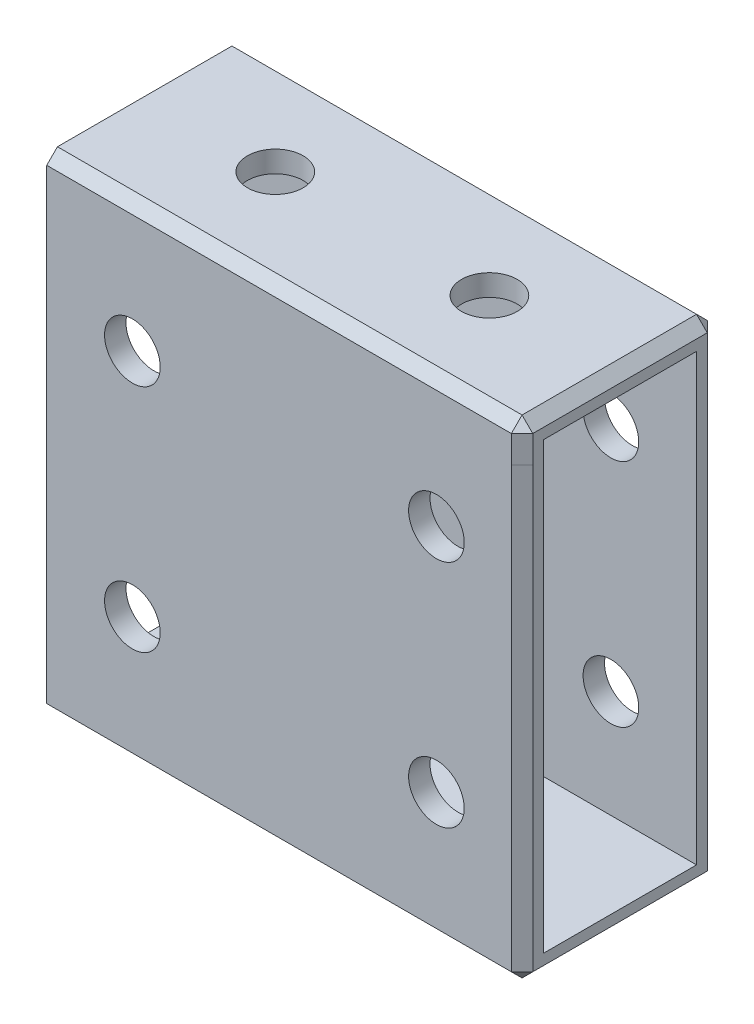
SolidWorks part; units mm, degrees
ref_plane "Front Plane" through (0, 0, 0) normal (0, 0, 1) x (1, 0, 0)
ref_plane "Top Plane" through (0, 0, 0) normal (0, 1, 0) x (1, 0, 0)
ref_plane "Right Plane" through (0, 0, 0) normal (1, 0, 0) x (0, 0, -1)
sketch "Sketch1" plane through (0, 0, 0) normal (0, 0, 1) x (1, 0, 0)
  line L0 (22.2, 40) -> (22.2, 0) construction
  line L1 (0, 0) -> (44.4, 0)
  line L2 (0, 0) -> (0, 40)
  line L3 (0, 40) -> (44.4, 40)
  line L4 (44.4, 0) -> (44.4, 40)
  line L5 (0, 0) -> (8, 0) construction
  line L6 (0, 0) -> (0, 8) construction
  line L10 (8, 29.9769) -> (8, 27.3769) construction
  line L11 (8, 19) -> (8, 8.4769) construction
  line L12 (8, 19) -> (10.573, 19) construction
  line L15 (10.573, 19) -> (10.573, 40) construction
  line L16 (8, 8.4769) -> (36.4, 8.4769) construction
  line L17 (36.4, 8.4769) -> (36.4, 29.9769) construction
  circle A0 centre (8, 8.4769) radius 2.6
  circle A1 centre (8, 29.9769) radius 2.6
  circle A2 centre (36.4, 29.9769) radius 2.6
  circle A3 centre (36.4, 8.4769) radius 2.6
  dimension "D5" = 5.2
  dimension "D6" = 5.2
  dimension "D7" = 5.2
  dimension "D8" = 5.2
  dimension "D1" = 44.4
  dimension "D2" = 40
  dimension "D3" = 21.5
  dimension "D4" = 21.5
  dimension "D9" = 21
  dimension "D10" = 8
  dimension "D11" = 8
extrude "Boss-Extrude1" add sketch "Sketch1" along normal blind 2
sketch "Sketch2" plane through (0, 40, 0) normal (0, 1, 0) x (1, 0, 0)
  line L0 (44.4, -2) -> (44.4, 0) construction
  line L1 (0, -2) -> (44.4, -2)
  line L2 (0, -2) -> (0, 16.3)
  line L3 (0, 16.3) -> (44.4, 16.3)
  line L4 (44.4, -2) -> (44.4, 16.3)
  dimension "D1" = 18.3
  dimension "D2" = 44.4
extrude "Boss-Extrude2" add sketch "Sketch2" along normal blind 2
pattern_linear "LPattern1" count 2 spacing 16.3 along (0, 0, -1) of "Boss-Extrude1"
sketch "Sketch3" plane through (0, 42, 0) normal (0, 1, 0) x (1, 0, 0)
  line L0 (22.2, 16.3) -> (22.2, -2) construction
  line L1 (44.4, 16.3) -> (0, 16.3) construction
  line L2 (0, -2) -> (44.4, -2) construction
  line L3 (22.2, 7.15) -> (12.2, 7.15) construction
  line L4 (22.2, 7.15) -> (32.2, 7.15) construction
  circle A0 centre (12.2, 7.15) radius 2.6
  circle A1 centre (32.2, 7.15) radius 2.6
  dimension "D3" = 5.2
  dimension "D4" = 5.2
  dimension "D1" = 10
  dimension "D2" = 10
extrude "Cut-Extrude1" cut sketch "Sketch3" against normal through all
chamfer "Chamfer1" distance 1 angle 45 11 edges at (22.2, 42, -16.3) (22.2, 42, 2) (0, 0, -15.3) (0, 0, 1) (22.2, 0, 2) (44.4, 0, 1) (44.4, 21, 2) (44.4, 42, -7.15) (44.4, 21, -16.3) (44.4, 0, -15.3) (22.2, 0, -16.3)
sketch "Sketch4" plane through (0, 0, 2) normal (0, 0, 1) x (1, 0, 0)
  line L3 (36.4, 8.4769) -> (36.4, 29.9769) construction
  line L4 (36.4, 19.2269) -> (1, 19.2269) construction
ref_plane "Plane1" through (0, 19.2269, 0) normal (0, 1, 0) x (1, 0, 0)
mirror "Mirror1" about plane through (0, 19.2269, 0) normal (0, 1, 0) of "LPattern1", "Boss-Extrude2", "Boss-Extrude1"
chamfer "Chamfer3" distance 1 angle 45 5 edges at (44.4, 17.4538, 2) (44.4, 17.4538, -16.3) (44.4, -3.5462, -7.15) (22.2, -3.5462, 2) (22.2, -3.5462, -16.3)
